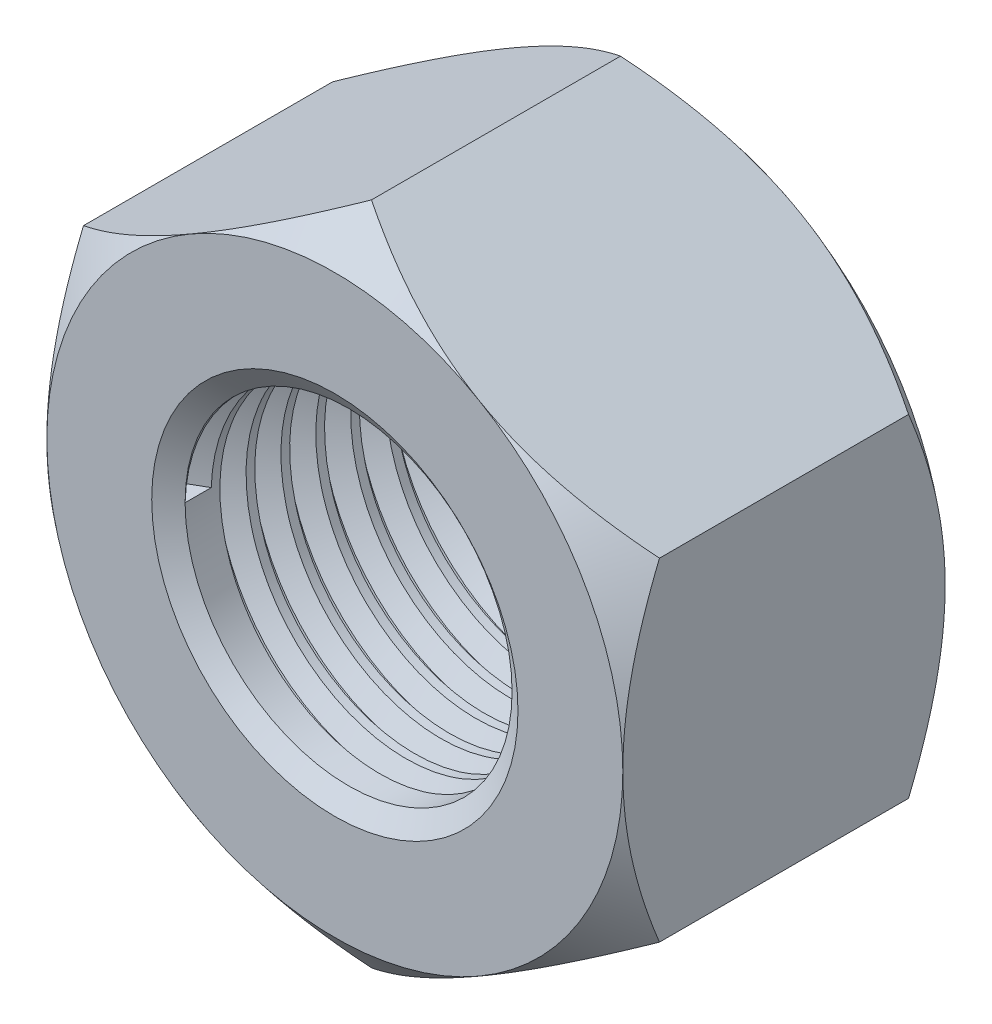
SolidWorks part; units mm, degrees
extrude "BaseNut" add sketch "BaseNutSke" against normal blind 9.779
sketch "BaseNutSke" plane through (0, 0, 0) normal (0, 0, 1) x (1, 0, 0)
  line L6 (8.7376, 5.0447) -> (8.7376, -5.0447)
  line L7 (-8.7376, 5.0447) -> (-8.7376, -5.0447)
  line L8 (8.7376, 5.0447) -> (0, 10.0893)
  line L9 (0, 10.0893) -> (-8.7376, 5.0447)
  line L10 (-8.7376, -5.0447) -> (0, -10.0893)
  line L11 (0, -10.0893) -> (8.7376, -5.0447)
  circle A0 centre (0, 0) radius 4.9606
  dimension "D2" = 8.7376
  dimension "D3" = 8.7376
  dimension "D1" = 120
  dimension "D4" = 8.7376
cosmetic thread "ThreadCosmetic" [suppressed] parameters "Thread_major"=11.1125
pattern_linear "ThdSchPat" [suppressed]
revolve "ThreadSchematic" [suppressed] cut sketch "ThdSchSke" angle 360 about L6
sketch "ThdSchSke" plane through (0, 0, 0) normal (0, 1, 0) x (1, 0, 0)
  line L0 (-5.5562, 0.0254) -> (-4.9606, 0.4425)
  line L1 (-4.9606, 0.4425) -> (-2.4803, 0.4425)
  line L2 (-2.4803, 0.4425) -> (-2.4803, -0.3917)
  line L3 (-2.4803, -0.3917) -> (-4.9606, -0.3917)
  line L4 (-4.9606, -0.3917) -> (-5.5562, 0.0254)
  line L5 (-3.175, 1.27) -> (3.175, 1.27) construction
  line L6 (0, 1.27) -> (0, -2.9874) construction
  line L7 (0, 9.3365) -> (0, 0.4171) construction
  dimension "SideAngle" = 55
  dimension "Advance" = 1.27
  dimension "D1" = 0.0254
ref_plane "Plane1" through (0, 0, 0) normal (0, 0, 1) x (1, 0, 0)
ref_plane "Plane2" through (0, 0, 0) normal (0, 1, 0) x (1, 0, 0)
ref_plane "Plane3" through (0, 0, 0) normal (1, 0, 0) x (0, 0, -1)
sketch "Sketch4" plane through (0, 0, 0) normal (1, 0, 0) x (0, 0, -1)
  line L0 (9.779, 8.7376) -> (9.3726, 8.7376)
  line L1 (9.779, 8.7376) -> (9.779, 22.7893)
  line L2 (9.3726, 22.7893) -> (9.779, 22.7893)
  line L3 (9.3726, 22.7893) -> (9.3726, 8.7376)
  line L4 (0, 0) -> (34.925, 0) construction
  line L6 (9.779, 5.0447) -> (9.779, 10.0893) construction
  line L7 (0, 8.7376) -> (-12.7, 8.7376)
  line L8 (0, 5.0447) -> (0, 10.0893) construction
  line L9 (1.1112, 10.0893) -> (1.1113, 22.7893)
  line L10 (1.1113, 22.7893) -> (-12.7, 22.7893)
  line L11 (-12.7, 22.7893) -> (-12.7, 8.7376)
  line L12 (0, 8.7376) -> (1.1112, 10.0893)
  line L14 (0, 5.0447) -> (0, -5.0447) construction
  line L15 (9.779, 10.0893) -> (0, 10.0893) construction
  dimension "D1" = 8.7376
  dimension "D2" = 1.1113
  dimension "D3" = 12.7
  dimension "D4" = 12.7
revolve "Bearing-Face" [suppressed] cut sketch "Sketch4" angle 360 about L4
sketch "Sketch3" plane through (0, 0, 0) normal (1, 0, 0) x (0, 0, -1)
  line L0 (9.779, 8.7376) -> (8.6677, 10.0893)
  line L1 (8.6677, 10.0893) -> (8.6677, 22.7893)
  line L2 (8.6677, 22.7893) -> (22.479, 22.7893)
  line L3 (22.479, 22.7893) -> (22.479, 8.7376)
  line L4 (22.479, 8.7376) -> (9.779, 8.7376)
  line L5 (9.779, 5.0447) -> (9.779, 10.0893) construction
  line L6 (9.779, 10.0893) -> (0, 10.0893) construction
  line L7 (0, 0) -> (38.6776, 0) construction
  line L8 (9.779, 0) -> (0, 0) construction
  line L9 (4.8895, 10.0893) -> (4.8895, 44.222) construction
  line L10 (1.1113, 22.7893) -> (-12.7, 22.7893)
  line L11 (-12.7, 22.7893) -> (-12.7, 8.7376)
  line L12 (-12.7, 8.7376) -> (0, 8.7376)
  line L13 (0, 8.7376) -> (1.1113, 10.0893)
  line L14 (1.1113, 10.0893) -> (1.1113, 22.7893)
  line L16 (9.779, 10.0893) -> (0, 10.0893) construction
  dimension "D1" = 8.7376
  dimension "D2" = 1.1113
  dimension "D4" = 12.7
  dimension "D3" = 12.7
revolve "Double-Chamfer" cut sketch "Sketch3" angle 360 about L7
sketch "Sketch5" plane through (0, 0, 0) normal (1, 0, 0) x (0, 0, -1)
  line L0 (9.7536, 5.5562) -> (9.2948, 4.9011)
  line L1 (9.8044, 5.5563) -> (9.7536, 5.5562)
  line L2 (9.8044, 5.5563) -> (9.8044, 4.9011)
  line L3 (9.8044, 4.9011) -> (9.2948, 4.9011)
  line L6 (-0.0508, 5.5562) -> (0, 5.5562)
  line L7 (0, 5.5562) -> (0.4588, 4.9011)
  line L9 (0.4588, 4.9011) -> (-0.0508, 4.9011)
  line L10 (-0.0508, 4.9011) -> (-0.0508, 5.5562)
  line L11 (25.0375, 0) -> (38.388, 0) construction
  line L12 (9.779, 0) -> (0, 0) construction
  dimension "D1" = 35
  dimension "D2" = 0.0508
  dimension "ThreadMajor" = 5.5562
  dimension "Offset1" = 9.8044
revolve "EndChamfer" cut sketch "Sketch5" angle 360 about L11
thread "Thread1" pitch 1.0583 method cut profile "Thread Profile1" start angle 0, offset 0, length 0, pitch 1.0583, diameter 9.9212
ref_plane "Plane4" through (-4.9606, 0, -0.4171) normal (0, -1, 0) x (-1, 0, 0)
sketch "Thread Profile1" plane through (-4.9606, 0, -0.4171) normal (0, -1, 0) x (-1, 0, 0)
  line L0 (0, 0) -> (0, 1.0583) construction
  line L1 (0, 0) -> (0.5728, 0.3307)
  line L2 (0.5728, 0.3307) -> (0.5728, 0.463)
  line L3 (0.5728, 0.463) -> (0, 0.7937)
  line L4 (0.5728, 0.3969) -> (0, 0.3969) construction
  line L11 (0, 0) -> (0, 0.7937)
  point P2 (0, 0)
  dimension "Pitch" = 1.0583
  dimension "Profile_Angle" = 60
  dimension "Profile_Land" = 0.1323
  dimension "Profile_Height" = 0.5728
equation "\"D2@BaseNutSke\" = \"Width_flats@BaseNutSke\" / 2"
equation "\"D3@BaseNutSke\" = \"Width_flats@BaseNutSke\" / 2"
equation "\"D1@Sketch3\" = \"Width_flats@BaseNutSke\" /2"
equation "\"D2@Sketch3\" = \"Thread_major@ThreadCosmetic\" *.1"
equation "\"D1@Sketch4\" = \"D2@BaseNutSke\""
equation "\"D2@Sketch4\" = \"Thread_major@ThreadCosmetic\" *.10"
equation "\"D4@BaseNutSke\" = \"D3@BaseNutSke\""
equation "\"Thread_major@ThdSchSke\" = \"Thread_major@ThreadCosmetic\""
equation "\"Tap_Drill@ThdSchSke\" = \"Tap_drill@BaseNutSke\""
equation "\"OverCut@ThdSchSke\" = \"Tap_Drill@ThdSchSke\" * 0.5"
equation "\"Num_threads@ThdSchPat\" = int(  ( \"Thickness@BaseNut\" - 0.002 ) / \"Advance@ThdSchSke\" + 0.999 )  + 1"
equation "\"Advance@ThdSchPat\" = ( \"Thickness@BaseNut\" - 0.002 ) /  (\"Num_threads@ThdSchPat\" - 1) 'relax it"
equation "' \"Num_threads@ThdSchPat\" = \"Num_threads@ThdSchPat\" - sgn( \"Num_threads@ThdSchPat\" - 1) '---chamfered tips only---"
equation "\"ThreadMajor@Sketch5\" = \"Thread_major@ThreadCosmetic\" * 0.5"
equation "\"ChamferDepth@Sketch5\" = (\"Thread_major@ThreadCosmetic\" - \"Tap_drill@BaseNutSke\") * 0.55"
equation "\"Offset1@Sketch5\" = \"Thickness@BaseNut\" + 0.001"
equation "\"Offset2@Sketch5\" = \"Offset1@Sketch5\" + 0.002"
